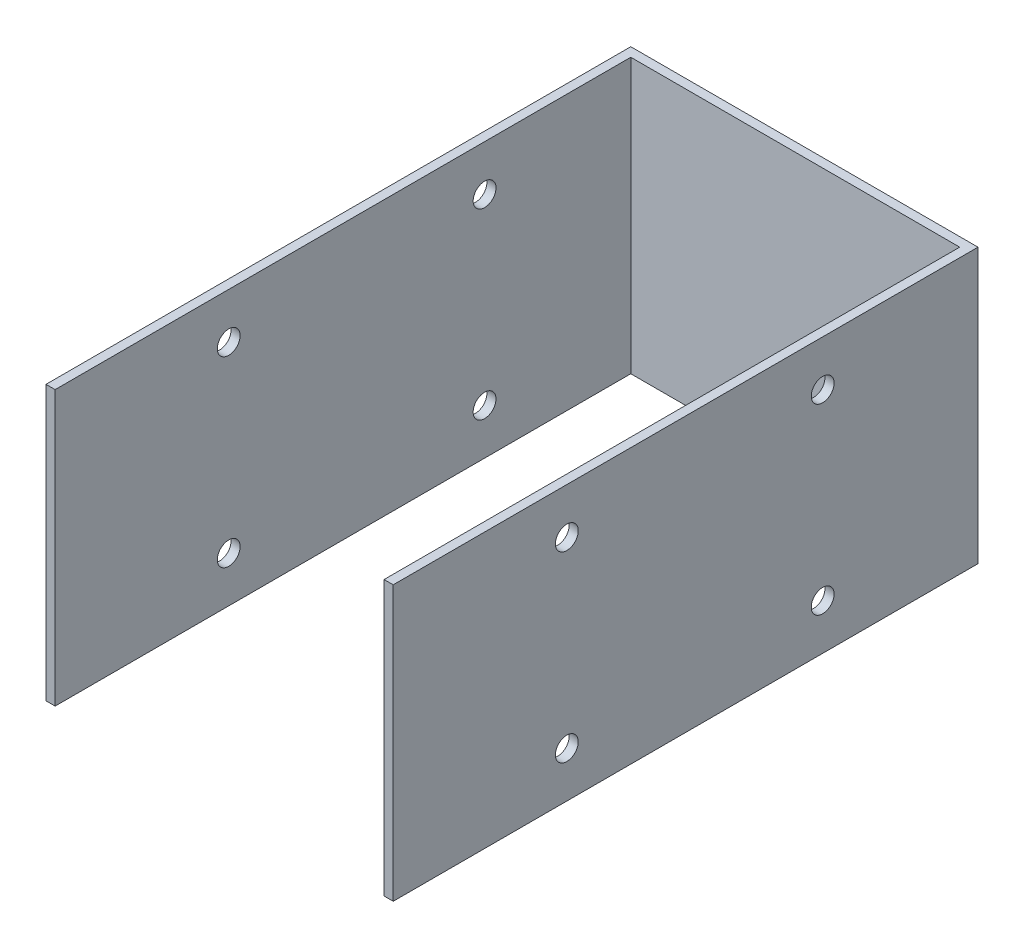
SolidWorks part; units mm, degrees
ref_plane "Ebene vorne" through (0, 0, 0) normal (0, 0, 1) x (1, 0, 0)
ref_plane "Ebene oben" through (0, 0, 0) normal (0, 1, 0) x (1, 0, 0)
ref_plane "Ebene rechts" through (0, 0, 0) normal (1, 0, 0) x (0, 0, -1)
sketch "Sketch1" plane through (0, 0, 0) normal (0, 1, 0) x (1, 0, 0)
  line L0 (0, 0) -> (0, 64)
  line L1 (0, 64) -> (38, 64)
  line L2 (38, 64) -> (38, 0)
  line L3 (1, 0) -> (1, 63)
  line L4 (1, 63) -> (37, 63)
  line L5 (37, 63) -> (37, 0)
  line L6 (0, 0) -> (1, 0)
  line L7 (38, 0) -> (37, 0)
  dimension "D1" = 64
  dimension "D2" = 38
  dimension "D3" = 1
extrude "Boss-Extrude1" add sketch "Sketch1" along normal blind 30
hole_wizard "M3 Tapped Hole1" positions "Sketch3" profile "Sketch4" tap size "M3" standard "DIN" end condition up to next
sketch "Sketch3" plane through (0, 0, 0) normal (-1, 0, 0) x (0, 0, 1)
  line L0 (-64, 15) -> (0, 15) construction
  line L1 (-64, 30) -> (-64, 0) construction
  line L2 (0, 30) -> (0, 0) construction
  point P0 (-47, 5)
  point P2 (-47, 25)
  point P4 (-19, 25)
  point P6 (-19, 5)
  point P15 (0, 0)
  point P16 (0, 0)
  point P17 (0, 0)
  point P18 (-24.0638, 19.8717)
  point P19 (0, 0)
  point P20 (-23.9459, 19.4788)
  point P21 (0, 0)
  point P22 (0, 0)
  point P23 (0, 0)
  point P24 (0, 0)
  point P25 (-22.728, 22.1504)
  dimension "D1" = 17
  dimension "D2" = 28
  dimension "D3" = 20
sketch "Sketch4" plane through (0, 5, -47) normal (0, 1, 0) x (0, 0, 1)
  line L0 (0, 0) -> (0, 38)
  line L1 (0, 38) -> (1.25, 38)
  line L2 (1.25, 38) -> (1.25, 0)
  line L5 (1.25, 0) -> (0, 0)
  line L11 (0, -6.35) -> (0, 107.95) construction
  dimension "Thru Tap Drill Dia." = 2.5
  dimension "Thru Tap Drill Depth" = 38
cosmetic thread "Hole Thread1" parameters "D2"=3
cosmetic thread "Hole Thread2" parameters "D2"=3
cosmetic thread "Hole Thread3" parameters "D2"=3
cosmetic thread "Hole Thread4" parameters "D2"=3
ref_plane "Plane1" through (19, 0, 0) normal (-1, 0, 0) x (0, 0, 1)
mirror "Mirror1" about plane through (19, 0, 0) normal (-1, 0, 0) of "M3 Tapped Hole1"
ref_plane "Plane2" through (0, 15, 0) normal (0, 1, 0) x (1, 0, 0)
ref_axis "Axis2" through (19, 15, 3.2) along (0, 0, -1)
